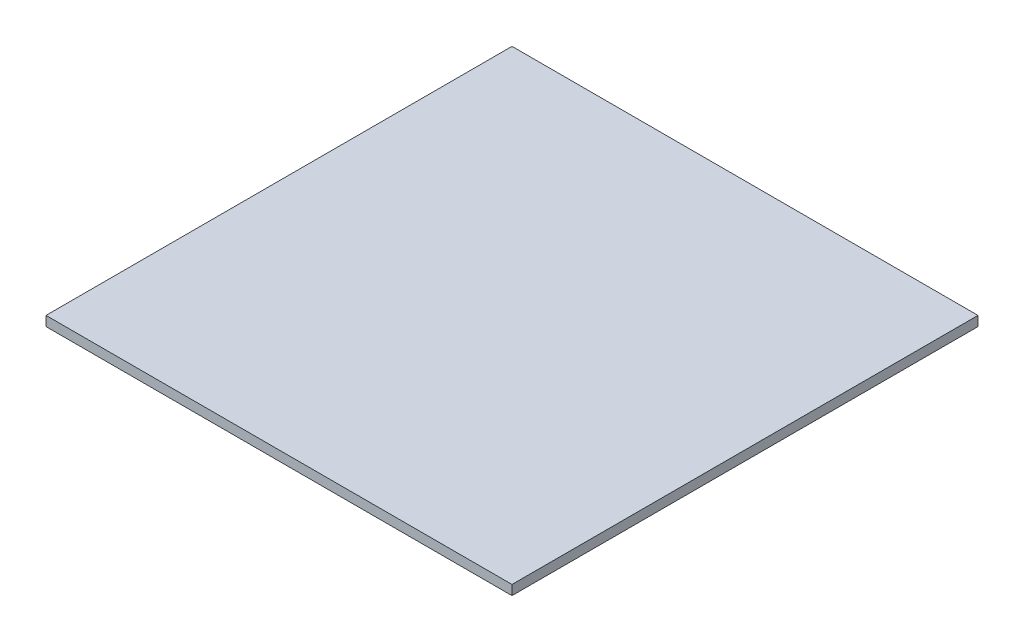
SolidWorks part; units mm, degrees
material "Cedar"
ref_plane "Front Plane" through (0, 0, 0) normal (0, 0, 1) x (1, 0, 0)
ref_plane "Top Plane" through (0, 0, 0) normal (0, 1, 0) x (1, 0, 0)
ref_plane "Right Plane" through (0, 0, 0) normal (1, 0, 0) x (0, 0, -1)
sketch "Sketch1" plane through (0, 0, 0) normal (0, 1, 0) x (1, 0, 0)
  line L1 (0, 0) -> (609.6, 0)
  line L2 (0, 0) -> (0, 609.6)
  line L3 (0, 609.6) -> (609.6, 609.6)
  line L4 (609.6, 0) -> (609.6, 609.6)
  dimension "D1" = 609.6
  dimension "D2" = 609.6
extrude "Boss-Extrude1" add sketch "Sketch1" along normal blind 12.7
